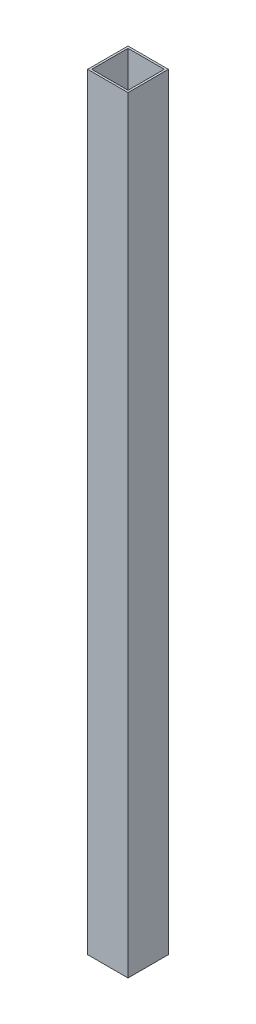
SolidWorks part; units mm, degrees
ref_plane "Front Plane" through (0, 0, 0) normal (0, 0, 1) x (1, 0, 0)
ref_plane "Top Plane" through (0, 0, 0) normal (0, 1, 0) x (1, 0, 0)
ref_plane "Right Plane" through (0, 0, 0) normal (1, 0, 0) x (0, 0, -1)
sketch "Sketch1" plane through (0, 0, 0) normal (0, 1, 0) x (1, 0, 0)
  line L0 (0, 0) -> (0, 25.4)
  line L1 (0, 25.4) -> (25.4, 25.4)
  line L2 (25.4, 25.4) -> (25.4, 0)
  line L3 (25.4, 0) -> (0, 0)
  line L6 (1.27, 12.3615) -> (1.27, 24.13)
  line L7 (1.27, 24.13) -> (12.7, 24.13)
  line L10 (12.7, 24.13) -> (24.13, 24.13)
  line L11 (24.13, 24.13) -> (24.13, 12.7)
  line L12 (24.13, 1.27) -> (24.13, 12.7)
  line L13 (24.13, 1.27) -> (12.7, 1.27)
  line L14 (1.27, 1.27) -> (12.7, 1.27)
  line L15 (1.27, 12.3615) -> (1.27, 1.27)
  point P5 (0, 0)
  point P7 (0, 0)
  point P9 (0, 0)
  dimension "D1" = 25.4
  dimension "D2" = 25.4
  dimension "D3" = 11.7685
  dimension "D4" = 11.0915
  dimension "D5" = 11.43
  dimension "D6" = 11.43
extrude "Boss-Extrude1" add sketch "Sketch1" along normal blind 482.6
